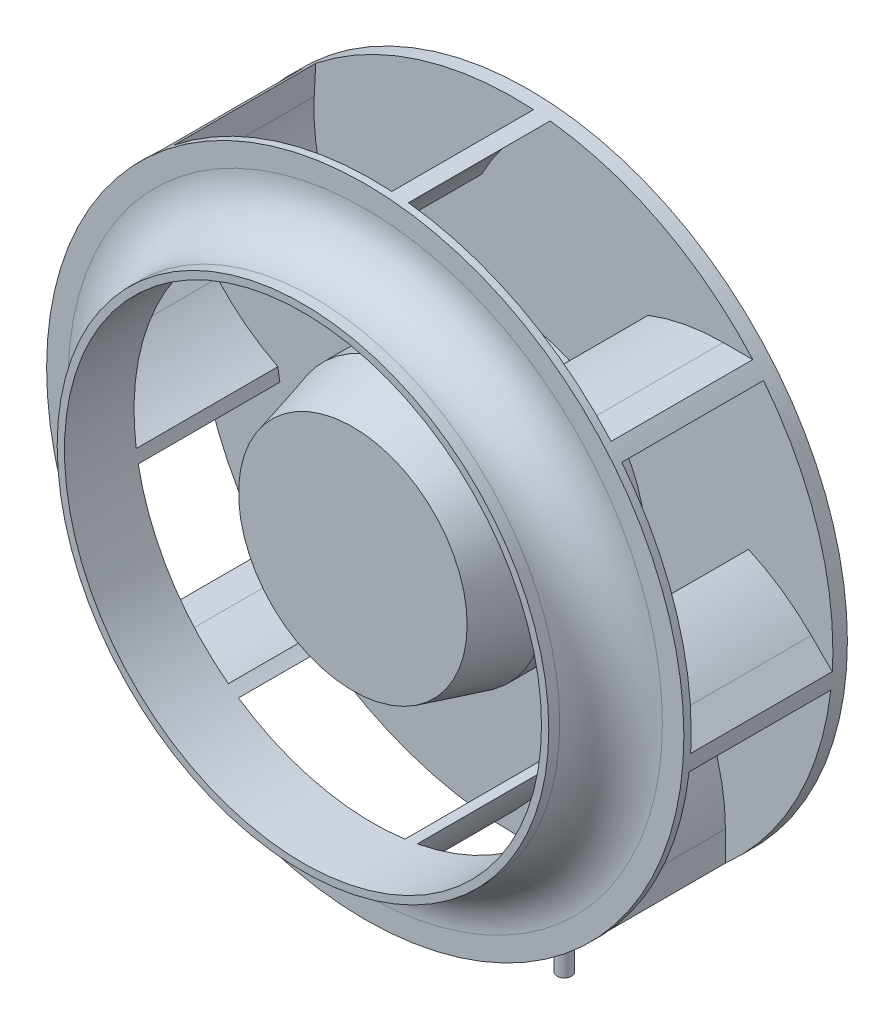
SolidWorks part; units mm, degrees
ref_plane "Front Plane" through (0, 0, 0) normal (0, 0, 1) x (1, 0, 0)
ref_plane "Top Plane" through (0, 0, 0) normal (0, 1, 0) x (1, 0, 0)
ref_plane "Right Plane" through (0, 0, 0) normal (1, 0, 0) x (0, 0, -1)
sketch "Sketch1" plane through (0, 0, 0) normal (1, 0, 0) x (0, 0, -1)
  line L0 (0, 0) -> (0, 36)
  line L1 (0, 36) -> (-7, 36)
  line L2 (-7, 36) -> (-7, 87.5)
  line L3 (-7, 87.5) -> (-51.9037, 87.5)
  line L4 (-51.9037, 87.5) -> (-51.9037, 81.5963)
  line L5 (-66, 67.5) -> (-69, 67.5)
  line L6 (-69, 67.5) -> (-69, 65.5)
  line L7 (-69, 65.5) -> (-11, 65.5)
  line L8 (-11, 65.5) -> (-11, 36)
  line L9 (-11, 36) -> (-38.0578, 36)
  line L10 (-38.0578, 36) -> (-55.3, 31.38)
  line L11 (-55.3, 31.38) -> (-55.3, 0)
  line L12 (-55.3, 0) -> (0, 0)
  line L13 (0, 0) -> (38.022, 0) construction
  arc A0 (-51.9037, 81.5963) -> (-66, 67.5) centre (-66, 81.5963) cw
  dimension "D2" = 175
  dimension "D3" = 72
  dimension "D4" = 72
  dimension "D5" = 15
  dimension "D6" = 55.3
  dimension "D7" = 7
  dimension "D8" = 62
  dimension "D9" = 131
  dimension "D10" = 2
  dimension "D11" = 4.62
  dimension "D12" = 4
  dimension "D13" = 3
  dimension "D14" = 17.0963
  dimension "D15" = 69
revolve "Revolve1" add sketch "Sketch1" angle 360 about L13
sketch "Sketch2" plane through (0, 0, 11) normal (0, 0, 1) x (1, 0, 0)
  line L0 (75.5686, 58) -> (57.393, 58)
  line L1 (75.5686, 58) -> (17.3488, 93.6676)
  line L2 (17.3488, 93.6676) -> (3.8418, 81.5058)
  line L3 (-15.119, 37) -> (13.0124, 37)
  arc A0 (57.393, 58) -> (13.0124, 37) centre (57.393, 0.6038) ccw
  arc A1 (3.8418, 81.5058) -> (-15.119, 37) centre (42.2473, 38.8521) ccw
  circle A2 centre (0, 0) radius 81.5963 construction
  dimension "D1" = 42
  dimension "D2" = 58
  dimension "D3" = 1
extrude "Cut-Extrude1" cut sketch "Sketch2" along normal offset from surface (38.9037 mm away) 2 up to face at (81.5963, 0, 51.9037)
ref_axis "Axis1" through (0, 0, -21.4836) along (0, 0, 1)
pattern_circular "CirPattern1" count 8 over 360 about axis through (0, 0, -21.4836) along (0, 0, 1) of "Cut-Extrude1"
sketch "Sketch3" plane through (0, 0, 0) normal (1, 0, 0) x (0, 0, -1)
  line L0 (5.8, -29.6497) -> (5.8, -53)
  line L1 (5.8, -53) -> (4.8, -54)
  line L2 (4.8, -54) -> (4.8, -127.3079)
  line L3 (4.8, -127.3079) -> (2.8, -127.3079)
  line L4 (2.8, -127.3079) -> (2.8, -29.6497)
  line L5 (2.8, -29.6497) -> (5.8, -29.6497)
  line L6 (2.8, -29.6497) -> (2.8, -17.2563) construction
  dimension "D1" = 6
  dimension "D2" = 4
  dimension "D3" = 54
  dimension "D4" = 2.8
  dimension "D5" = 45
revolve "Revolve2" add sketch "Sketch3" angle 360 about L6
